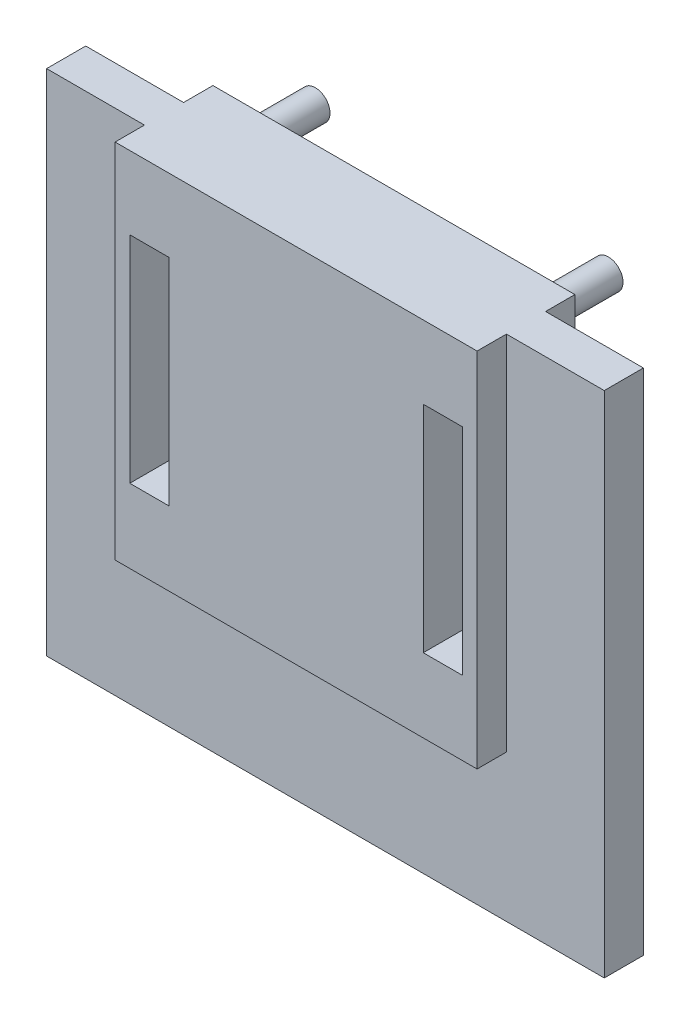
SolidWorks part; units mm, degrees
ref_plane "Front Plane" through (0, 0, 0) normal (0, 0, 1) x (1, 0, 0)
ref_plane "Top Plane" through (0, 0, 0) normal (0, 1, 0) x (1, 0, 0)
ref_plane "Right Plane" through (0, 0, 0) normal (1, 0, 0) x (0, 0, -1)
sketch "Sketch1" plane through (0, 0, 0) normal (0, 0, 1) x (1, 0, 0)
  line L1 (28.5, -26) -> (-28.5, -26)
  line L2 (28.5, -26) -> (28.5, 26)
  line L3 (28.5, 26) -> (-28.5, 26)
  line L4 (-28.5, -26) -> (-28.5, 26)
  line L5 (28.5, -26) -> (-28.5, 26) construction
  line L6 (28.5, 26) -> (-28.5, -26) construction
  point P0 (0, 0)
  dimension "D1" = 57
  dimension "D2" = 52
extrude "Boss-Extrude1" add sketch "Sketch1" along normal blind 4
sketch "Sketch3" plane through (0, 0, 4) normal (0, 0, 1) x (1, 0, 0)
  line L0 (28.5, 26) -> (-28.5, 26) construction
  line L5 (-18.5, 26) -> (18.5, 26)
  line L6 (-18.5, 26) -> (-18.5, -11)
  line L7 (-18.5, -11) -> (18.5, -11)
  line L8 (18.5, 26) -> (18.5, -11)
  line L9 (-28.5, -26) -> (28.5, -26) construction
  line L10 (-28.5, 26) -> (-28.5, -26) construction
  dimension "D1" = 37
  dimension "D2" = 37
  dimension "D3" = 10
  dimension "D4" = 15
extrude "Boss-Extrude2" add sketch "Sketch3" along normal blind 3 contours L6 L5 L8 L7
sketch "Sketch4" plane through (0, 0, 0) normal (0, 0, -1) x (-1, 0, 0)
  line L0 (28.5, 26) -> (28.5, -26) construction
  line L1 (-18.5, 26) -> (18.5, 26)
  line L2 (-18.5, 26) -> (-18.5, -11)
  line L3 (-18.5, -11) -> (18.5, -11)
  line L4 (18.5, 26) -> (18.5, -11)
  dimension "D1" = 37
  dimension "D2" = 37
  dimension "D3" = 10
extrude "Boss-Extrude3" add sketch "Sketch4" along normal blind 3
sketch "Sketch6" plane through (0, 0, 0) normal (0, 0, 1) x (1, 0, 0)
  circle A0 centre (-15.0288, 22.5432) radius 1.5
  circle A1 centre (14.9183, 22.5432) radius 1.5
  circle A2 centre (-15.0288, -7.5144) radius 1.5
  circle A3 centre (14.9183, -7.5144) radius 1.5
  dimension "D9" = 3
  dimension "D10" = 3
  dimension "D11" = 3
  dimension "D12" = 3
extrude "Boss-Extrude4" add sketch "Sketch6" against normal blind 10 contours A1 | A3
extrude "Boss-Extrude6" add sketch "Sketch6<6>" against normal blind 10
sketch "Sketch6<6>" plane through (0, 0, 0) normal (0, 0, 1) x (1, 0, 0) same geometry as "Sketch6"
sketch "Sketch8" plane through (0, 0, -3) normal (0, 0, -1) x (-1, 0, 0)
  line L0 (-18.5, 26) -> (-18.5, -11) construction
  line L1 (-17, 18.5432) -> (-13, 18.5432)
  line L2 (-17, 18.5432) -> (-17, -3.4568)
  line L3 (-17, -3.4568) -> (-13, -3.4568)
  line L4 (-13, 18.5432) -> (-13, -3.4568)
  line L5 (13, 18.5432) -> (17, 18.5432)
  line L6 (13, 18.5432) -> (13, -3.4568)
  line L7 (13, -3.4568) -> (17, -3.4568)
  line L8 (17, 18.5432) -> (17, -3.4568)
  line L9 (18.5, 26) -> (18.5, -11) construction
  line L10 (-18.5, -11) -> (18.5, -11) construction
  line L11 (18.5, 26) -> (-18.5, 26) construction
  circle A0 centre (-14.9183, 22.5432) radius 1.5 construction
  circle A1 centre (15.0288, 22.5432) radius 1.5 construction
  circle A3 centre (-14.9183, -7.5144) radius 1.5 construction
  circle A4 centre (-14.9183, 22.5432) radius 1.5 construction
  dimension "D7" = 4
  dimension "D8" = 4
  dimension "D9" = 3.4856
  dimension "D10" = 3.4568
  dimension "D1" = 4
  dimension "D2" = 4
  dimension "D3" = 1.5
  dimension "D4" = 1.5
  dimension "D5" = 22
  dimension "D6" = 22
extrude "Cut-Extrude1" cut sketch "Sketch8" against normal through all
